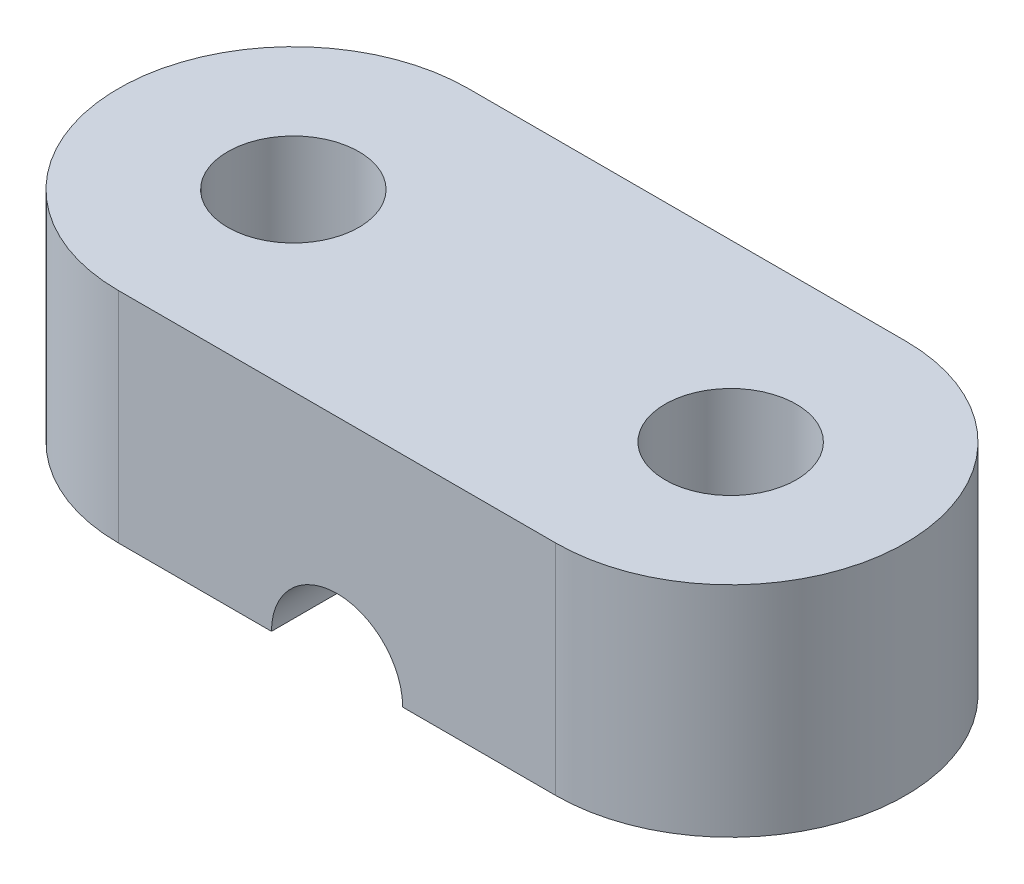
SolidWorks part; units mm, degrees
material "Nylon 101"
ref_plane "Front" through (0, 0, 0) normal (0, 0, 1) x (1, 0, 0)
ref_plane "Top" through (0, 0, 0) normal (0, 1, 0) x (1, 0, 0)
ref_plane "Right" through (0, 0, 0) normal (1, 0, 0) x (0, 0, -1)
sketch "Sketch2" plane through (0, 0, 0) normal (0, 1, 0) x (1, 0, 0)
  line L0 (-5, 0) -> (5, 0) construction
  line L1 (-5, 4) -> (5, 4)
  line L2 (-5, -4) -> (5, -4)
  arc A0 (-5, 4) -> (-5, -4) centre (-5, 0) ccw
  arc A1 (5, -4) -> (5, 4) centre (5, 0) ccw
  circle A2 centre (-5, 0) radius 1.5
  circle A3 centre (5, 0) radius 1.5
  point P3 (0, 0)
  dimension "D2" = 4
  dimension "D3" = 3
  dimension "D1" = 10
extrude "Boss-Extrude1" add sketch "Sketch2" along normal blind 5
sketch "Sketch3" plane through (0, 0, 4) normal (0, 0, 1) x (1, 0, 0)
  line L0 (-5, 0) -> (5, 0) construction
  circle A0 centre (0, 0) radius 1.5
  dimension "D1" = 3
extrude "Cut-Extrude1" cut sketch "Sketch3" against normal through all
